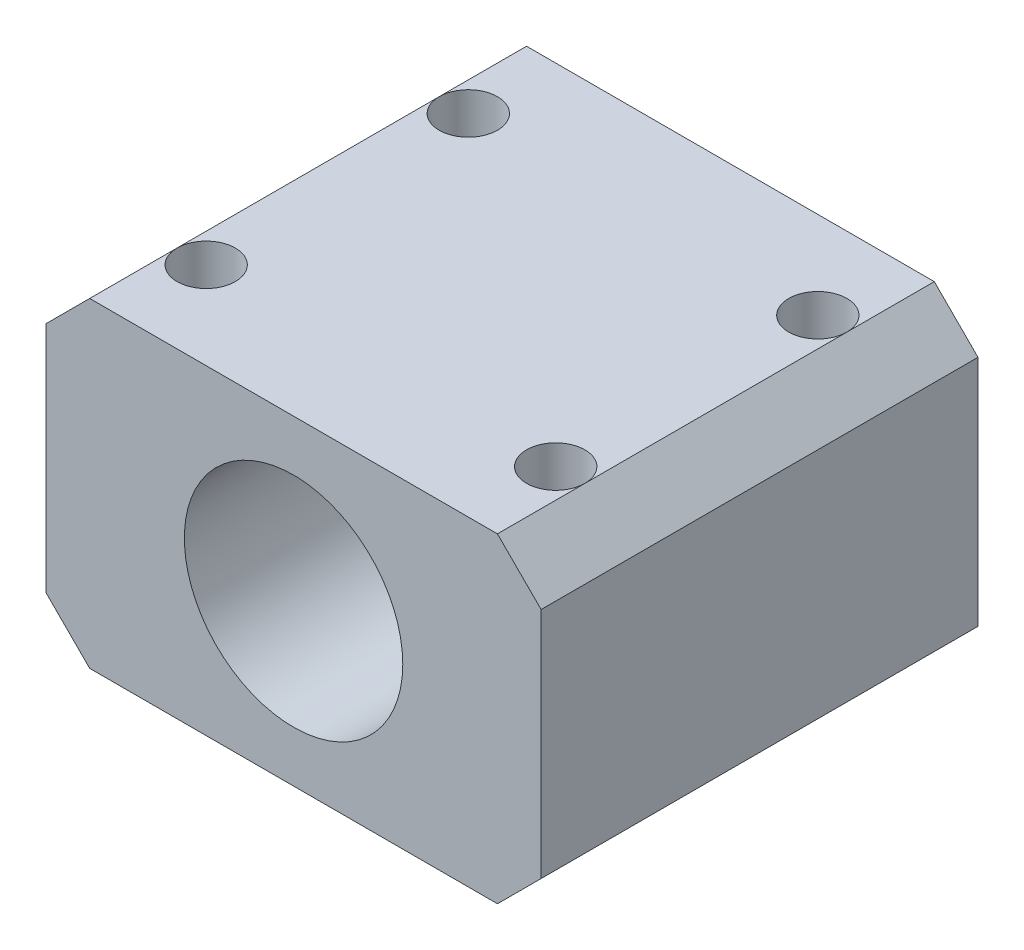
SolidWorks part; units mm, degrees
ref_plane "Alzado" through (0, 0, 0) normal (0, 0, 1) x (1, 0, 0)
ref_plane "Planta" through (0, 0, 0) normal (0, 1, 0) x (1, 0, 0)
ref_plane "Vista lateral" through (0, 0, 0) normal (1, 0, 0) x (0, 0, -1)
sketch "Croquis1" plane through (0, 0, 0) normal (0, 0, 1) x (1, 0, 0)
  line L0 (-17, 0) -> (17, 0)
  line L1 (17, 0) -> (17, -22)
  line L4 (17, -22) -> (-17, -22)
  line L5 (0, -22) -> (0, 0) construction
  line L8 (-17, 0) -> (-17, -22)
  circle A0 centre (0, -11) radius 7.5
  dimension "D3" = 11
  dimension "D5" = 15
  dimension "D1" = 17
  dimension "D2" = 22
extrude "Saliente-Extruir1" add sketch "Croquis1" along normal blind 30
sketch "Croquis2" plane through (0, 0, 0) normal (0, 1, 0) x (1, 0, 0)
  line L0 (-17, -15) -> (17, -15) construction
  line L1 (-17, 0) -> (17, 0) construction
  line L2 (-17, 0) -> (-17, -30) construction
  line L3 (-17, -30) -> (17, -30) construction
  line L4 (17, 0) -> (17, -30) construction
  line L5 (-12, -6) -> (12, -24) construction
  line L6 (-12, -24) -> (-12, -6) construction
  line L7 (-12, -6) -> (12, -6) construction
  line L8 (12, -6) -> (12, -24) construction
  line L9 (12, -24) -> (-12, -24) construction
  circle A0 centre (-12, -6) radius 2
  circle A1 centre (12, -6) radius 2
  circle A2 centre (-12, -24) radius 2
  circle A3 centre (12, -24) radius 2
  point P16 (0, -15)
  point P17 (0, -15)
  point P18 (10.8492, -5.1837)
  dimension "D1" = 4
  dimension "D2" = 4
  dimension "D3" = 4
  dimension "D4" = 4
  dimension "D5" = 18
  dimension "D6" = 24
extrude "Cortar-Extruir1" cut sketch "Croquis2" against normal blind 30
chamfer "Chaflán1" distance 3 angle 45 4 edges at (-17, 0, 15) (17, 0, 15) (-17, -22, 15) (17, -22, 15)
